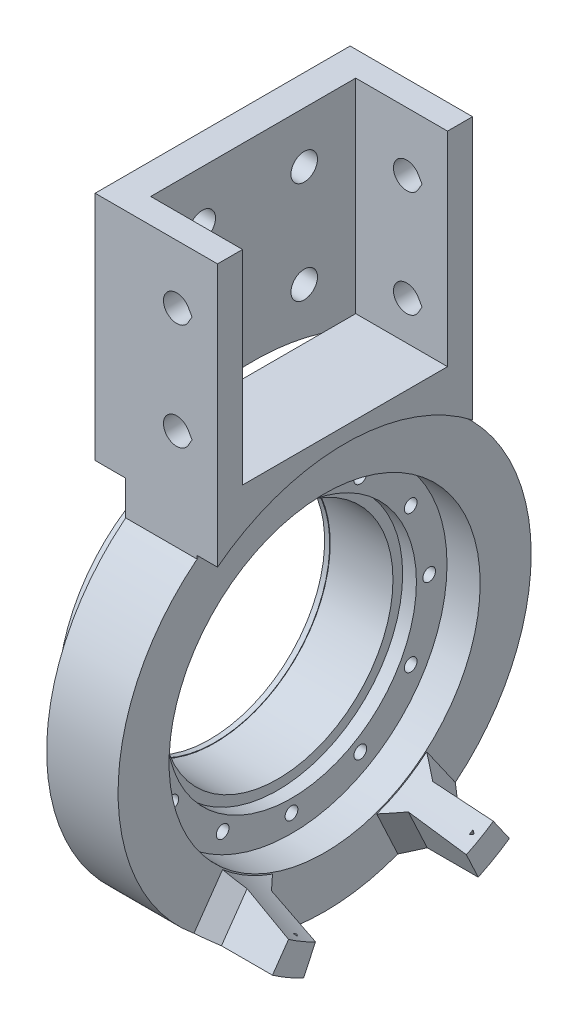
SolidWorks part; units mm, degrees
ref_plane "Front Plane" through (0, 0, 0) normal (0, 0, 1) x (1, 0, 0)
ref_plane "Top Plane" through (0, 0, 0) normal (0, 1, 0) x (1, 0, 0)
ref_plane "Right Plane" through (0, 0, 0) normal (1, 0, 0) x (0, 0, -1)
sketch "Sketch1" plane through (0, 0, 0) normal (1, 0, 0) x (0, 0, -1)
  line L0 (0, 27) -> (0, 0) construction
  circle A0 centre (0, 0) radius 29.75
  circle A1 centre (0, 0) radius 24.5
  circle A2 centre (0, 0) radius 27 construction
  circle A3 centre (0, 27) radius 1.25
  circle A4 centre (13.5, 23.3827) radius 1.25
  circle A5 centre (23.3827, 13.5) radius 1.25
  circle A6 centre (27, 0) radius 1.25
  circle A7 centre (23.3827, -13.5) radius 1.25
  circle A8 centre (13.5, -23.3827) radius 1.25
  circle A9 centre (0, -27) radius 1.25
  circle A10 centre (-13.5, -23.3827) radius 1.25
  circle A11 centre (-23.3827, -13.5) radius 1.25
  circle A12 centre (-27, 0) radius 1.25
  circle A13 centre (-23.3827, 13.5) radius 1.25
  circle A14 centre (-13.5, 23.3827) radius 1.25
  point P31 (0, 0)
  dimension "D1" = 59.5
  dimension "D2" = 49
  dimension "D3" = 54
  dimension "D4" = 2.5
  dimension "D5" = 12
extrude "Boss-Extrude1" add sketch "Sketch1" against normal blind 16 contours A1 | A0 A14 A13 A12 A11 A10 A9 A8 A7 A6 A5 A4 A3 A1 region at (0, 0, 28.9085) region at (0, 0, 0)
extrude "Cut-Extrude1" cut sketch "Sketch1<3>" against normal blind 2.7 contours A1 region at (0, 0, 0)
sketch "Sketch1<3>" plane through (0, 0, 0) normal (1, 0, 0) x (0, 0, -1) same geometry as "Sketch1"
sketch "Sketch2" plane through (-2.7, 0, 0) normal (1, 0, 0) x (0, 0, -1)
  circle A0 centre (0, 0) radius 22.6
  dimension "D1" = 45.2
extrude "Cut-Extrude2" cut sketch "Sketch2" against normal through all
sketch "Sketch3" plane through (0, 0, 0) normal (1, 0, 0) x (0, 0, -1)
  circle A0 centre (0, 0) radius 40.5
  circle A1 centre (0, 0) radius 29.75
  dimension "D1" = 81
  dimension "D2" = 59.5
extrude "Boss-Extrude2" add sketch "Sketch3" along normal blind 6.5 separate body
extrude "Boss-Extrude3" add sketch "Sketch3<2>" against normal blind 7.5
sketch "Sketch3<2>" plane through (0, 0, 0) normal (1, 0, 0) x (0, 0, -1) same geometry as "Sketch3"
ref_plane "Plane1" through (-1.5, 0, 0) normal (1, 0, 0) x (0, 0, -1)
sketch "Sketch4" plane through (-1.5, 0, 0) normal (1, 0, 0) x (0, 0, -1)
  line L0 (0, 0) -> (0, 84) construction
  line L1 (-23, 40.5) -> (23, 40.5) construction
  line L2 (-23, 84) -> (23, 84)
  line L3 (-23, 84) -> (-23, 33.3354)
  line L5 (23, 84) -> (23, 33.3354)
  circle A0 centre (0, 0) radius 40.5 construction
  circle A2 centre (0, 0) radius 40.5
  arc A3 (23, 33.3354) -> (-23, 33.3354) centre (0, 0) ccw
  point P13 (0, 40.5)
  dimension "D1" = 46
  dimension "D2" = 23
  dimension "D3" = 43.5
sketch "Sketch5" plane through (-7.5, 0, 0) normal (-1, 0, 0) x (0, 0, 1)
  circle A0 centre (0, 0) radius 32.25
  circle A1 centre (0, 0) radius 29.75
  dimension "D1" = 59.5
  dimension "D2" = 64.5
extrude "Boss-Extrude5" add sketch "Sketch5" along normal blind 1
sketch "Sketch6" plane through (-7.5, 0, 0) normal (1, 0, 0) x (0, 0, -1)
  line L0 (25, 44) -> (-25, 44)
  line L2 (-25, 44) -> (-25, 31.863)
  line L3 (25, 44) -> (25, 31.863)
  line L5 (0, 44) -> (0, 0) construction
  circle A1 centre (0, 0) radius 40.5 construction
  arc A3 (-25, 31.863) -> (25, 31.863) centre (0, 0) cw
  point P3 (0, 44)
  circle M13 centre (0, 0) radius 40.5
  dimension "D1" = 44
  dimension "D2" = 50
extrude "Boss-Extrude6" add sketch "Sketch6" along normal blind 18 contours L0 | L0 L3 L2 M13 | L3 A3 L2 L0 region at (-7.5, 37.9315, -24.4855)
sketch "Sketch7" plane through (0, 44, 0) normal (0, 1, 0) x (1, 0, 0)
  line L0 (10.5, 25) -> (10.5, -25) construction
  line L1 (-7.5, 25) -> (10.5, 25)
  line L2 (-7.5, 25) -> (-7.5, 20.1)
  line L3 (-7.5, 20.1) -> (10.5, 20.1)
  line L4 (10.5, 25) -> (10.5, 20.1)
  line L6 (-7.5, -25) -> (10.5, -25)
  line L7 (-7.5, -25) -> (-7.5, -20.1)
  line L8 (-7.5, -20.1) -> (10.5, -20.1)
  line L9 (10.5, -25) -> (10.5, -20.1)
  dimension "D1" = 4.9
  dimension "D2" = 4.9
extrude "Boss-Extrude7" add sketch "Sketch7" along normal blind 40
sketch "Sketch8" plane through (0, 0, 25) normal (0, 0, 1) x (1, 0, 0)
  line L0 (-7.5, 84) -> (-7.5, 31.863) construction
  line L1 (2.5, 51.6108) -> (2.5, 72.4832) construction
  line L2 (2.5, 51.6108) -> (10.5, 51.6108) construction
  line L3 (10.5, 84) -> (10.5, 31.863) construction
  line L4 (2.5, 72.4832) -> (10.5, 72.4832) construction
  line L5 (4.7533, 73.7803) -> (5.5, 72.4832)
  line L6 (5.5, 72.4832) -> (4.7533, 71.1861)
  line L7 (4.7533, 52.9079) -> (5.5, 51.6108)
  line L8 (5.5, 51.6108) -> (4.7533, 50.3137)
  circle A0 centre (2.5, 72.4832) radius 2.6
  circle A1 centre (2.5, 51.6108) radius 2.6
  dimension "D1" = 5.2
  dimension "D2" = 5.2
  dimension "D3" = 10
  dimension "D4" = 3
  dimension "D5" = 3
extrude "Cut-Extrude3" cut sketch "Sketch8" against normal through all contours A0 | A0 L6 L5 | A1 | A1 L8 L7 region at (5.1867, 72.4832, 25) region at (2.5, 72.4832, 25) region at (5.1867, 51.6108, 25) region at (2.5, 51.6108, 25)
sketch "Sketch9" plane through (-7.5, 0, 0) normal (-1, 0, 0) x (0, 0, 1)
  line L0 (-10, 84) -> (-10, 30.6604) construction
  line L5 (-25, 84) -> (-25, 38.6135)
  line L6 (-25, 84) -> (25, 84)
  line L7 (25, 84) -> (25, 38.6135)
  line L8 (25, 84) -> (25, 31.863) construction
  line L9 (10, 84) -> (10, 30.6604) construction
  line L10 (-10, 54) -> (10, 54) construction
  line L11 (10, 74) -> (-10, 74) construction
  line L12 (-25, 84) -> (-20.1, 84) construction
  line L13 (-25, 84) -> (-25, 31.863) construction
  arc A1 (-25, 38.6135) -> (25, 38.6135) centre (0, 0) cw
  circle A2 centre (0, 0) radius 32.25 construction
  circle A3 centre (0, 0) radius 32.25 construction
  circle A4 centre (-10, 74) radius 2.6
  circle A5 centre (10, 74) radius 2.6
  circle A6 centre (-10, 54) radius 2.6
  circle A7 centre (10, 54) radius 2.6
  dimension "D1" = 46
  dimension "D6" = 5.2
  dimension "D7" = 5.2
  dimension "D8" = 5.2
  dimension "D9" = 5.2
  dimension "D2" = 15
  dimension "D3" = 15
  dimension "D4" = 10
  dimension "D5" = 20
extrude "Boss-Extrude9" add sketch "Sketch9" along normal blind 6 contours A1 | A1 L6 | A1 region at (-7.5, 63.7421, 0)
sketch "Sketch10" plane through (-7.5, 0, 0) normal (-1, 0, 0) x (0, 0, 1)
  line L0 (-25, 62) -> (25, 62) construction
  line L1 (-25, 38.6135) -> (-25, 31.863) construction
  line L2 (25, 38.6135) -> (25, 31.863) construction
  line L3 (-25, 42) -> (25, 42) construction
  line L4 (25, 84) -> (25, 38.6135) construction
  line L5 (-25, 84) -> (-20.1, 84) construction
  line L6 (-20.1, 84) -> (-20.1, 44) construction
  circle A0 centre (-22.6, 62) radius 0.9
  circle A1 centre (-22.6, 42) radius 0.9
  circle A2 centre (22.5, 62) radius 0.9
  circle A3 centre (22.5, 42) radius 0.9
  dimension "D3" = 1.8
  dimension "D5" = 1.8
  dimension "D7" = 2.5
  dimension "D8" = 1.8
  dimension "D9" = 1.8
  dimension "D10" = 2.5
  dimension "D1" = 22
  dimension "D2" = 20
  dimension "D4" = 2.5
  dimension "D6" = 2.5
extrude "Cut-Extrude4" [suppressed] cut sketch "Sketch10" against normal blind 10
sketch "Sketch11" plane through (6.5, 0, 0) normal (1, 0, 0) x (0, 0, -1)
  circle A0 centre (0, 0) radius 30.5
  dimension "D1" = 61
extrude "Cut-Extrude5" cut sketch "Sketch11" against normal blind 6.5
sketch "Sketch12" plane through (-16, 0, 0) normal (-1, 0, 0) x (0, 0, 1)
  circle A0 centre (0, 0) radius 29.75
  circle A1 centre (0, 0) radius 22.5
extrude "Boss-Extrude10" add sketch "Sketch12" against normal blind 1
sketch "Sketch13" plane through (10.5, 0, 0) normal (1, 0, 0) x (0, 0, -1)
  circle A0 centre (0, 0) radius 41
  dimension "D1" = 82
extrude "Cut-Extrude6" cut sketch "Sketch13" against normal blind 4
ref_axis "Axis1" through (-7.5, 0, 0) along (1, 0, 0)
ref_plane "Plane3" through (0, 0, 0) normal (0, 0.5, 0.866) x (1, 0, 0)
sketch "Sketch15" plane through (0, -60.75, 35.074) normal (0, -0.5, -0.866) x (1, 0, 0)
  line L1 (6.5, -110.6481) -> (6.5, -29.6481) construction
  line L2 (0, -70.1481) -> (-16, -70.1481) construction
  line L3 (-16, -40.3981) -> (-16, -99.8981) construction
  line L4 (6.5, -39.3981) -> (19.5, -35.1481)
  line L5 (19.5, -35.1481) -> (19.5, -29.6481)
  line L6 (19.5, -29.6481) -> (6.5, -29.6481)
  line L7 (6.5, -29.6481) -> (6.5, -39.3981)
  dimension "D1" = 5.5
  dimension "D2" = 13
  dimension "D3" = 9.75
revolve "Revolve1" add sketch "Sketch15" angle 5 about L2 other way angle 5
ref_plane "Plane2" through (0, -35.074, 20.25) normal (0, -0.866, 0.5) x (1, 0, 0)
sketch "Sketch19" plane through (0, -35.074, 20.25) normal (0, -0.866, 0.5) x (1, 0, 0)
  line L0 (19.5, -3.0505) -> (19.5, 3.0505) construction
  line L1 (16.58, 0) -> (19.5, 0) construction
  line L2 (19.5, -3.5298) -> (19.5, 3.5298) construction
  line L3 (17.4024, 0.9414) -> (18.48, 0)
  line L4 (18.48, 0) -> (17.4024, -0.9414)
  circle A0 centre (16.58, 0) radius 1.25
  dimension "D2" = 2.5
  dimension "D1" = 2.92
  dimension "D3" = 1.9
extrude "Cut-Extrude8" cut sketch "Sketch19" against normal blind 6 contours A0 | L1 A0 L4 | A0 L1 L3 region at (17.9885, -34.9471, 20.4699) region at (17.6859, -35.3252, 19.8149) region at (17.9885, -35.201, 20.0301)
ref_plane "Plane4" through (0, 0, 0) normal (0, 0.5, -0.866) x (1, 0, 0)
sketch "Sketch20" plane through (0, 0, 0) normal (0, 0.5, -0.866) x (1, 0, 0)
  line L0 (6.5, 40.5) -> (19.5, 40.5)
  line L1 (19.5, 40.5) -> (19.5, 35)
  line L2 (19.5, 35) -> (6.5, 30.75)
  line L3 (6.5, -40.5) -> (6.5, 40.5) construction
  line L4 (6.5, 30.75) -> (6.5, 40.5)
  dimension "D1" = 5.5
  dimension "D2" = 13
  dimension "D3" = 9.75
revolve "Revolve2" add sketch "Sketch20" angle 5 about axis through (-7.5, 0, 0) along (1, 0, 0) other way angle 5
ref_plane "Plane5" through (0, -35.074, -20.25) normal (0, -0.866, -0.5) x (-1, 0, 0)
sketch "Sketch21" plane through (0, -35.074, -20.25) normal (0, -0.866, -0.5) x (-1, 0, 0)
  line L0 (-16.58, 0) -> (0, 0) construction
  line L1 (-19.5, 3.5298) -> (-19.5, -3.5298) construction
  line L2 (-16.58, 0) -> (-19.5, 0) construction
  line L3 (-18.48, 0) -> (-17.4024, 0.9414)
  line L4 (-17.4024, -0.9414) -> (-18.48, 0)
  circle A0 centre (-16.58, 0) radius 1.25
  dimension "D2" = 2.5
  dimension "D1" = 2.92
  dimension "D3" = 1.9
extrude "Cut-Extrude9" cut sketch "Sketch21" against normal blind 6 contours A0 | A0 L3 L4 region at (17.9885, -35.074, -20.25) region at (16.58, -35.074, -20.25)
chamfer "Chamfer1" distance 3 angle 45 4 edges at (6.5, -29.1823, -20.4337) (6.5, -32.2872, -15.0558) (6.5, -32.2872, 15.0558) (6.5, -29.1823, 20.4337)
equation "\"D2@Sketch4\"=\"D1@Sketch4\"/2"
equation "\"D7@Sketch9\"=\"D6@Sketch9\""
equation "\"D8@Sketch9\"=\"D6@Sketch9\""
equation "\"D9@Sketch9\"=\"D6@Sketch9\""
